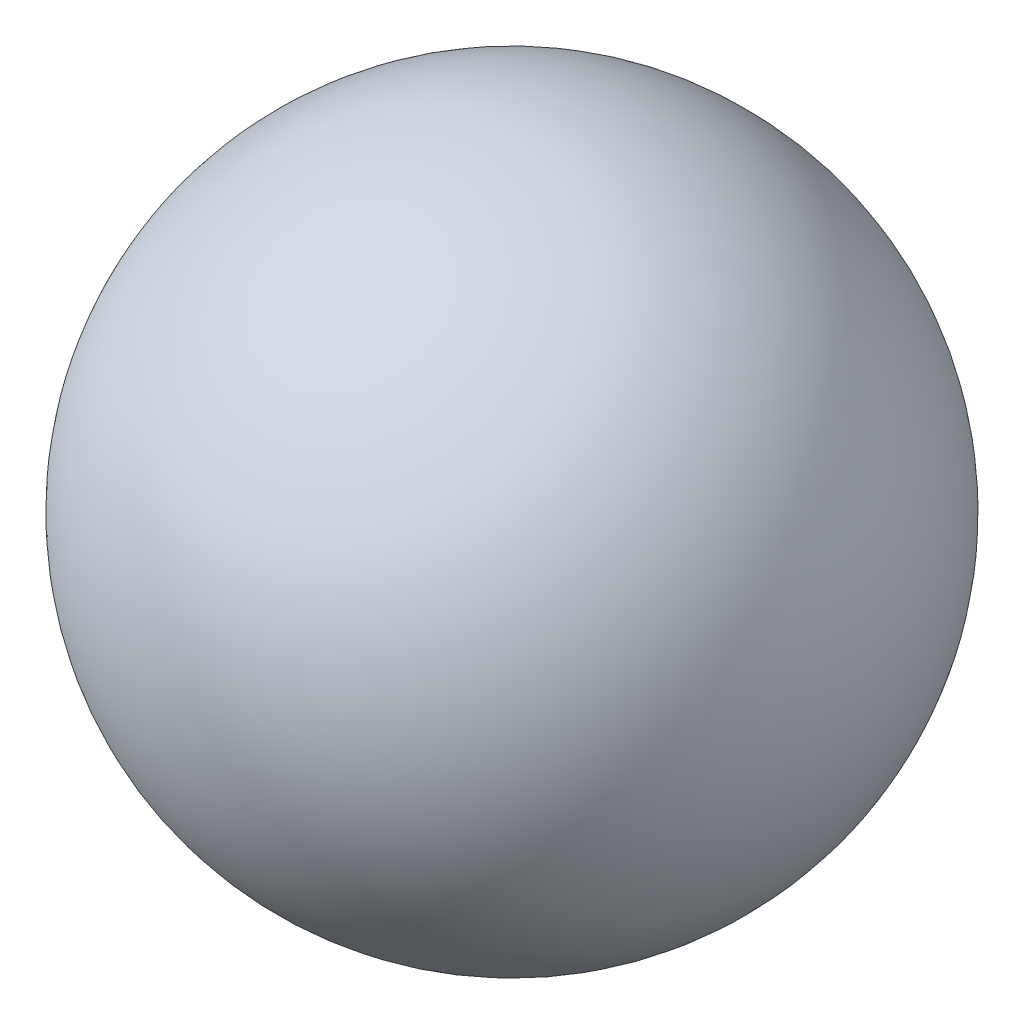
SolidWorks part; units mm, degrees
ref_plane "Front Plane" through (0, 0, 0) normal (0, 0, 1) x (1, 0, 0)
ref_plane "Top Plane" through (0, 0, 0) normal (0, 1, 0) x (1, 0, 0)
ref_plane "Right Plane" through (0, 0, 0) normal (1, 0, 0) x (0, 0, -1)
sketch "Sketch1" plane through (0, 0, 0) normal (0, 0, 1) x (1, 0, 0)
  line L0 (-3.2, 0) -> (3.2, 0)
  arc A0 (3.2, 0) -> (-3.2, 0) centre (0, 0) ccw
  dimension "D1" = 3.2
revolve "Revolve1" add sketch "Sketch1" angle 360 about L0
ref_axis "Axis1" through (-7.04, 0, 0) along (1, 0, 0)
